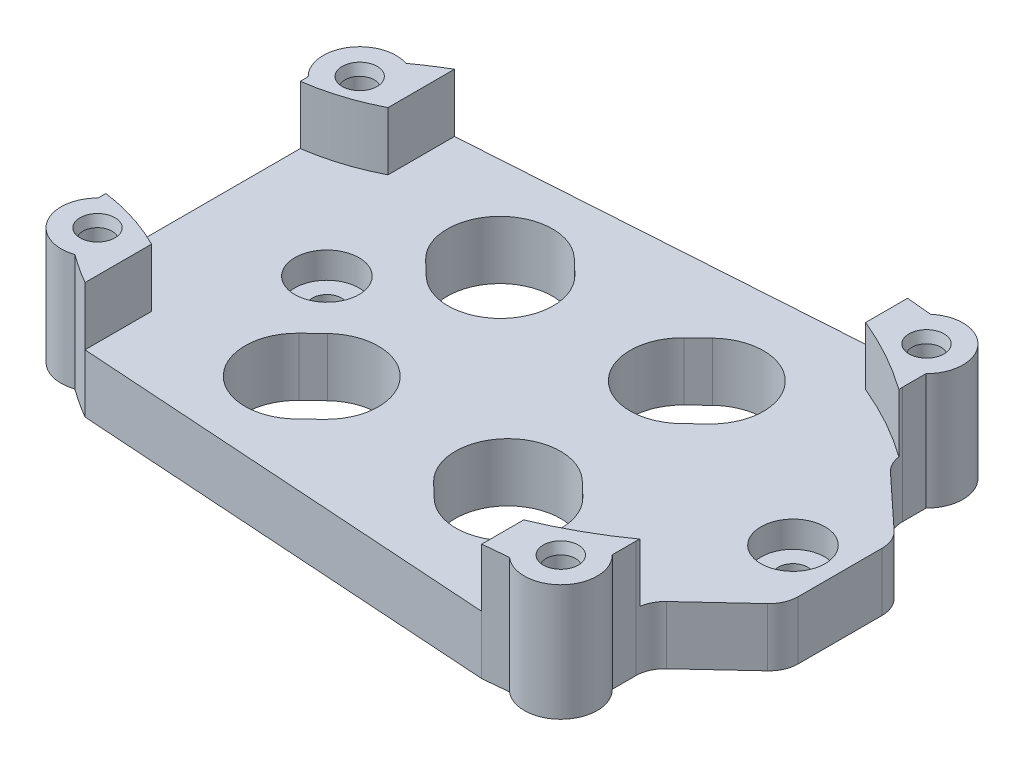
SolidWorks part; units mm, degrees
ref_plane "Front Plane" through (0, 0, 0) normal (0, 0, 1) x (1, 0, 0)
ref_plane "Top Plane" through (0, 0, 0) normal (0, 1, 0) x (1, 0, 0)
ref_plane "Right Plane" through (0, 0, 0) normal (1, 0, 0) x (0, 0, -1)
sketch "Sketch1" plane through (0, 0, 0) normal (0, 1, 0) x (1, 0, 0)
  line L0 (36.956, -25.685) -> (40.3201, -38.24) construction
  line L1 (36.956, -25.685) -> (46.656, -25.685) construction
  line L2 (24.8242, -41.435) -> (40.3201, -39.99)
  line L3 (42.0701, -13.13) -> (42.0701, -38.24)
  line L4 (36.956, -25.685) -> (4.956, -25.685) construction
  line L5 (4.956, -25.685) -> (4.956, -34.685) construction
  line L6 (7.7835, -33.245) -> (7.7835, -38.37)
  line L7 (3.206, -16.685) -> (3.206, -34.685)
  line L8 (36.956, -36.8813) -> (36.956, -40.3037)
  line L9 (36.956, -14.4887) -> (36.956, -11.0663)
  line L10 (24.8242, -9.935) -> (40.3201, -11.38)
  line L11 (7.7835, -18.125) -> (7.7835, -13)
  arc A8 (24.8242, -41.435) -> (25.4713, -41.3746) centre (24.8242, -37.935) ccw
  arc A13 (40.3201, -39.99) -> (42.0701, -38.24) centre (40.3201, -38.24) ccw
  arc A14 (4.956, -36.435) -> (24.8242, -41.435) centre (20.4556, -16.8196) ccw
  arc A15 (3.206, -34.685) -> (4.956, -36.435) centre (4.956, -34.685) ccw
  circle A16 centre (4.956, -34.685) radius 1
  circle A17 centre (40.3201, -38.24) radius 1
  circle A18 centre (24.8242, -37.935) radius 1
  arc A19 (36.956, -36.8813) -> (42.0701, -33.9697) centre (27.2302, -13.8507) ccw
  arc A20 (7.7835, -33.245) -> (3.206, -31.8522) centre (1.1844, -46.7154) ccw
  circle A21 centre (40.3201, -13.13) radius 1
  arc A22 (36.956, -14.4887) -> (42.0701, -17.4002) centre (27.2302, -37.5193) cw
  arc A23 (40.3201, -11.38) -> (42.0701, -13.13) centre (40.3201, -13.13) cw
  circle A24 centre (24.8242, -13.435) radius 1
  arc A25 (4.956, -14.935) -> (24.8242, -9.935) centre (20.4556, -34.5503) cw
  arc A26 (3.206, -16.685) -> (4.956, -14.935) centre (4.956, -16.685) cw
  circle A27 centre (4.956, -16.685) radius 1
  arc A28 (7.7835, -18.125) -> (3.206, -19.5177) centre (1.1844, -4.6546) cw
  arc A29 (4.956, -32.185) -> (4.91, -32.1854) centre (4.956, -34.685) ccw
  arc A30 (5.7673, -14.3203) -> (3.206, -18.4703) centre (4.956, -16.685) ccw
  arc A31 (3.206, -32.8996) -> (5.7673, -37.0497) centre (4.956, -34.685) ccw
  arc A32 (38.6969, -40.1414) -> (42.0701, -36.4546) centre (40.3201, -38.24) ccw
  arc A33 (42.0701, -14.9153) -> (38.6969, -11.2286) centre (40.3201, -13.13) ccw
  point P11 (42.0701, -25.685)
  point P50 (3.206, -25.685)
  dimension "D1" = 7
  dimension "D2" = 3.5
  dimension "D5" = 3.5
  dimension "D8" = 25
  dimension "D11" = 2
  dimension "D12" = 24.5
  dimension "D13" = 17.2459
  dimension "D14" = 2.8275
  dimension "D9" = 2
  dimension "D10" = 2
  dimension "D16" = 25
  dimension "D17" = 15
  dimension "D22" = 5
  dimension "D23" = 5
  dimension "D24" = 5
  dimension "D25" = 5
  dimension "D3" = 75
  dimension "D4" = 25.11
  dimension "D6" = 32
  dimension "D7" = 9
  dimension "D15" = 9.7
  dimension "D18" = 4.2703
  dimension "D19" = 3.4224
  dimension "D20" = 5.125
  dimension "D21" = 2.8327
extrude "Boss-Extrude1" add sketch "Sketch1" along normal blind 4 contours L11 A28 L7 A20 L6 A14 L2 L8 A19 L3 A22 L9 L10 A25 A18 A24 | A28 L11 A25 A26 L7 A27 | L6 A20 L7 A15 A14 A16 | A23 L10 L9 A22 L3 A21 | A19 L8 L2 A13 L3 A17 | L7 A31 A14 A15 | A25 A30 L7 A26 | L2 A32 L3 A13 | L3 A33 L10 A23 region at (23.1035, 0, 25.685) region at (6.8031, 0, 37.6675) region at (37.0374, 0, 38.5925) region at (2.8746, 0, 35.9696) region at (39.514, 0, 40.1249) region at (39.6393, 0, 15.7227) region at (3.2856, 0, 18.994) region at (42.1296, 0, 14.0227) region at (2.8746, 0, 15.4004)
extrude "Boss-Extrude2" add sketch "Sketch1<5>" along normal blind 8 contours L6 A20 L7 A15 A14 A16 | A23 L10 L9 A22 L3 A21 | A28 L11 A25 A26 L7 A27 | A19 L8 L2 A13 L3 A17 | A25 A30 L7 A26 | L7 A31 A14 A15 | L3 A33 L10 A23 | L2 A32 L3 A13 region at (6.8031, 0, 37.6675) region at (37.0374, 0, 38.5925) region at (2.8746, 0, 35.9696) region at (39.514, 0, 40.1249) region at (39.6393, 0, 15.7227) region at (3.2856, 0, 18.994) region at (42.1296, 0, 14.0227) region at (2.8746, 0, 15.4004)
sketch "Sketch1<5>" plane through (0, 0, 0) normal (0, 1, 0) x (1, 0, 0) same geometry as "Sketch1"
sketch "Sketch2" plane through (0, 4, 0) normal (0, 1, 0) x (1, 0, 0)
  line L8 (16.6451, -32.6328) -> (31.1244, -18.7372) construction
  line L9 (31.1261, -32.631) -> (16.6433, -18.739) construction
  line L10 (23.8847, -37.935) -> (23.8847, -13.435) construction
  line L12 (16.6451, -32.6328) -> (17.6335, -31.6842) construction
  line L13 (15.5303, -31.4712) -> (16.5187, -30.5226)
  line L14 (17.7599, -33.7944) -> (18.7483, -32.8458)
  line L15 (17.632, -19.6874) -> (16.6433, -18.739) construction
  line L16 (16.5175, -20.8493) -> (15.5288, -19.9009)
  line L17 (18.7465, -18.5255) -> (17.7578, -17.5771)
  line L18 (31.1244, -32.6328) -> (30.1359, -31.6842) construction
  line L19 (32.2392, -31.4712) -> (31.2507, -30.5226)
  line L20 (30.0096, -33.7944) -> (29.0211, -32.8458)
  line L21 (30.1375, -19.6874) -> (31.1261, -18.739) construction
  line L22 (31.2519, -20.8493) -> (32.2406, -19.9009)
  line L23 (29.023, -18.5255) -> (30.0117, -17.5771)
  line L24 (14.1455, -30.0282) -> (15.1339, -29.0796)
  line L25 (19.1447, -35.2374) -> (20.1331, -34.2888)
  line L26 (15.133, -22.2926) -> (14.1443, -21.3443)
  line L27 (20.1309, -17.0821) -> (19.1422, -16.1338)
  line L28 (32.6364, -22.2926) -> (33.6251, -21.3443)
  line L29 (27.6385, -17.0821) -> (28.6272, -16.1338)
  line L30 (33.624, -30.0282) -> (32.6355, -29.0796)
  line L31 (28.6247, -35.2374) -> (27.6363, -34.2888)
  line L32 (24.8242, -37.935) -> (24.8242, -36.935) construction
  arc A9 (15.5303, -31.4712) -> (17.7599, -33.7944) centre (16.6451, -32.6328) ccw
  arc A10 (18.7483, -32.8458) -> (16.5187, -30.5226) centre (17.6335, -31.6842) ccw
  arc A11 (16.5175, -20.8493) -> (18.7465, -18.5255) centre (17.632, -19.6874) ccw
  arc A12 (17.7578, -17.5771) -> (15.5288, -19.9009) centre (16.6433, -18.739) ccw
  arc A13 (32.2392, -31.4712) -> (30.0096, -33.7944) centre (31.1244, -32.6328) cw
  arc A14 (29.0211, -32.8458) -> (31.2507, -30.5226) centre (30.1359, -31.6842) cw
  arc A15 (31.2519, -20.8493) -> (29.023, -18.5255) centre (30.1375, -19.6874) cw
  arc A16 (30.0117, -17.5771) -> (32.2406, -19.9009) centre (31.1261, -18.739) cw
  arc A17 (20.1331, -34.2888) -> (15.1339, -29.0796) centre (17.6335, -31.6842) ccw
  arc A18 (14.1455, -30.0282) -> (19.1447, -35.2374) centre (16.6451, -32.6328) ccw
  arc A19 (19.1422, -16.1338) -> (14.1443, -21.3443) centre (16.6433, -18.739) ccw
  arc A20 (15.133, -22.2926) -> (20.1309, -17.0821) centre (17.632, -19.6874) ccw
  arc A21 (28.6272, -16.1338) -> (33.6251, -21.3443) centre (31.1261, -18.739) cw
  arc A22 (32.6364, -22.2926) -> (27.6385, -17.0821) centre (30.1375, -19.6874) cw
  arc A23 (27.6363, -34.2888) -> (32.6355, -29.0796) centre (30.1359, -31.6842) cw
  arc A24 (33.624, -30.0282) -> (28.6247, -35.2374) centre (31.1244, -32.6328) cw
  circle A25 centre (24.8242, -37.935) radius 1 construction
  point P3 (30.6301, -32.1585)
  point P4 (17.1376, -19.2132)
  point P13 (23.8847, -25.685)
  point P21 (30.6318, -19.2132)
  point P27 (23.8847, -25.685)
  point P29 (23.8847, -25.685)
  point P34 (17.1393, -32.1585)
  dimension "D4" = 12.9453
  dimension "D12" = 1.37
  dimension "D13" = 1.61
  dimension "D2" = 92.371
  dimension "D3" = 2
  dimension "D5" = 13.4942
  dimension "D6" = 24.5
  dimension "D7" = 0.9394
extrude "Cut-Extrude1" cut sketch "Sketch2" against normal blind 7 contours L26 A20 L27 A19 A12 L17 A11 L16 | A22 L28 A21 L29 L23 A16 L22 A15 | A16 L23 A15 L22 | A24 L30 A23 L31 L20 A14 L19 A13 | A14 L20 A13 L19 | L24 A18 L25 A17 A10 L14 A9 L13 | L14 A10 L13 A9 | L17 A12 L16 A11 region at (17.1393, 4, 32.1585) region at (30.6301, 4, 32.1585) region at (30.6318, 4, 19.2132) region at (14.7199, 4, 29.6374) region at (14.7189, 4, 21.7349) region at (27.6158, 4, 22.1062) region at (33.6454, 4, 35.0522)
sketch "Sketch4" plane through (0, 4, 0) normal (0, 1, 0) x (1, 0, 0)
  line L0 (42.0701, -17.4002) -> (46.9436, -21.935)
  line L1 (46.9436, -21.935) -> (46.9436, -29.435)
  line L2 (46.9436, -29.435) -> (42.0701, -33.9697)
  line L3 (42.0701, -17.4002) -> (42.0701, -33.9697)
  line L4 (42.4436, -33.685) -> (42.4436, -17.685) construction
  circle A0 centre (24.8242, -13.435) radius 1
  circle A1 centre (24.8242, -37.935) radius 1
  dimension "D3" = 2
  dimension "D1" = 7.5
  dimension "D2" = 4.5
extrude "Boss-Extrude3" add sketch "Sketch4" against normal up to surface (4 mm away) up to face at (17.1376, 0, 19.2132)
sketch "Sketch3" plane through (0, 4, 0) normal (0, 1, 0) x (1, 0, 0)
  line L0 (3.206, -25.685) -> (43.706, -25.685) construction
  line L1 (3.206, -19.5177) -> (3.206, -31.8522) construction
  circle A0 centre (11.706, -25.685) radius 2
  circle A1 centre (43.706, -25.685) radius 2
  dimension "D1" = 4
  dimension "D2" = 32
  dimension "D3" = 8.5
extrude "Cut-Extrude2" cut sketch "Sketch3" against normal blind 1.8
other "Move Face1" flip direction yes face at (39.556, 6, 35.501) face at (39.556, 6, 15.869) face at (5.5227, 6, 18.9132) face at (5.5227, 6, 32.4568) offset 0.5 parameters "D1"=0.5
other "Move Face2" flip direction yes face at (11.706, 2.2, 27.685) face at (43.706, 2.2, 27.685) offset 0.2 parameters "D1"=0.2
chamfer "Chamfer1" distance 0.7 distance2 0.2 2 edges at (4.956, 8, 17.685) (40.3201, 8, 14.13) first distance on face at (4.956, 0, 17.685) first distance on face at (40.3201, 0, 14.13)
chamfer "Chamfer2" distance 0.2 distance2 0.7 2 edges at (40.3201, 8, 39.24) (4.956, 8, 35.685) first distance on face at (39.7223, 8, 38.1374) first distance on face at (4.956, 8, 35.685)
ref_plane "Plane2" through (23.8847, 0, 0) normal (-1, 0, 0) x (0, 0, 1)
sketch "Sketch5" plane through (0, 4, 0) normal (0, 1, 0) x (1, 0, 0)
  line L0 (7.7835, -38.37) -> (36.956, -40.3037)
  line L1 (36.956, -40.3037) -> (18.4356, -45.1257)
  line L2 (18.4356, -45.1257) -> (7.7835, -38.37)
  line L3 (7.7835, -13) -> (36.956, -11.0663)
  line L4 (36.956, -11.0663) -> (18.4356, -6.2443)
  line L5 (18.4356, -6.2443) -> (7.7835, -13)
  line L6 (36.956, -40.3037) -> (38.6969, -40.1414) construction
  circle A0 centre (11.706, -25.685) radius 1
  circle A1 centre (43.706, -25.685) radius 1
  dimension "D1" = 2
  dimension "D2" = 10.6522
  dimension "D3" = 3.0816
extrude "Cut-Extrude3" cut sketch "Sketch5" against normal up to surface (4 mm away) up to face at (17.1376, 0, 19.2132)
fillet "Fillet1" radius 2 4 edges at (42.0701, 2, 17.4002) (42.0701, 2, 33.9697) (46.9436, 2, 29.435) (46.9436, 2, 21.935)
